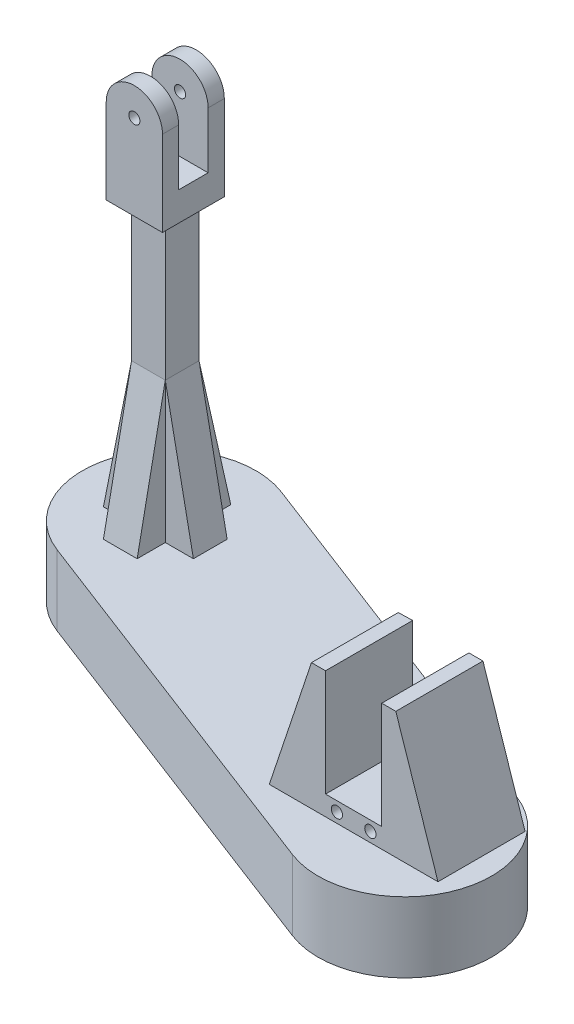
SolidWorks part; units mm, degrees
ref_plane "前基準面" through (0, 0, 0) normal (0, 0, 1) x (1, 0, 0)
ref_plane "上基準面" through (0, 0, 0) normal (0, 1, 0) x (1, 0, 0)
ref_plane "右基準面" through (0, 0, 0) normal (1, 0, 0) x (0, 0, -1)
sketch "草圖1" plane through (0, 0, 0) normal (0, 0, 1) x (1, 0, 0)
  line L0 (0, 0) -> (0, -11.05)
  line L1 (-10, 0) -> (-10, -30.2764)
  line L3 (10, -30.2764) -> (10, 0)
  line L4 (-10, -30.2764) -> (10, -30.2764)
  circle A1 centre (0, 0) radius 1.985
  arc A2 (10, 0) -> (-10, 0) centre (0, 0) ccw
  dimension "D1" = 11.05
  dimension "D2" = 3.97
  dimension "D3" = 20
extrude "填料-伸長1" add sketch "草圖1" along normal blind 12 contours L3 A2 L1 A1 region at (0, -11.3298, 0)
sketch "草圖2" plane through (10, 0, 0) normal (1, 0, 0) x (0, 0, -1)
  line L0 (-12, 0) -> (-9.1, 0)
  line L1 (-12, 0) -> (0, 0) construction
  line L2 (-12, 10) -> (-12, 0) construction
  line L3 (0, 0) -> (-2.9, 0)
  line L4 (-6, 0) -> (-3, 0)
  line L5 (-6, 0) -> (-9, 0)
  line L6 (-9, 0) -> (-9, 15.7808)
  line L7 (-9, 15.7808) -> (-3, 15.7808)
  line L8 (-3, 15.7808) -> (-3, 0)
  line L9 (-3, 0) -> (-3, -20)
  line L10 (-9, 0) -> (-8.6005, -20)
  line L11 (-8.6005, -20) -> (-3, -20)
  line M8 (0, 0) -> (-12, 0)
  dimension "D1" = 2.9
  dimension "D2" = 2.9
  dimension "D3" = 3
  dimension "D4" = 3
  dimension "D5" = 20
extrude "除料-伸長1" cut sketch "草圖2" against normal through all contours L8 L7 L6 M8 | L10 L11 L9 M8 region at (10, 7.8904, 6) region at (10, -9.8852, 5.9013)
sketch "草圖11" plane through (10, 0, 0) normal (1, 0, 0) x (0, 0, -1)
  line L0 (-9, 0) -> (-9, -20)
  line L1 (-9, -20) -> (-8.6005, -20)
  line L2 (-9, 0) -> (-8.6005, -20)
extrude "除料-伸長6" cut sketch "草圖11" against normal through all
sketch "草圖12" plane through (0, 0, 12) normal (0, 0, 1) x (1, 0, 0)
  line L0 (-10, 0) -> (-10, -30.2764)
  line L1 (-10, -30.2764) -> (10, -30.2764)
  line L2 (10, -30.2764) -> (10, 0)
  circle A0 centre (0, 0) radius 1.45
  circle A1 centre (0, 0) radius 10
  circle M1 centre (0, 0) radius 1.985
  line M2 (10, -30.2764) -> (10, 0)
  arc M3 (10, 0) -> (-10, 0) centre (0, 0) ccw
  line M4 (-10, 0) -> (-10, -30.2764)
  line M5 (-10, -30.2764) -> (10, -30.2764)
extrude "填料-伸長11" add sketch "草圖12" along normal blind 5 contours A1 M3 M1 | A1 M4 M5 M2 region at (0, -18.9541, 12) region at (0, 9.7172, 12)
sketch "草圖13" plane through (0, 0, 0) normal (0, 0, -1) x (-1, 0, 0)
  line L0 (-10, 0) -> (-10, -30.2764)
  line L1 (-10, -30.2764) -> (10, -30.2764)
  line L2 (10, 0) -> (10, -30.2764) construction
  line L3 (10, -30.2764) -> (-10, -30.2764) construction
  line L4 (10, -30.2764) -> (10, 0)
  circle A0 centre (0, 0) radius 1.45
  circle A1 centre (0, 0) radius 10
  circle M1 centre (0, 0) radius 1.985
  line M2 (-10, 0) -> (-10, -30.2764)
  line M3 (-10, -30.2764) -> (10, -30.2764)
  line M4 (10, -30.2764) -> (10, 0)
  arc M5 (10, 0) -> (-10, 0) centre (0, 0) ccw
extrude "填料-伸長12" add sketch "草圖13" along normal blind 5 contours A1 M5 M1 | A1 M2 M3 M4 region at (0, -18.9541, 0) region at (0, 9.7172, 0)
sketch "草圖14" plane through (-10, 0, 0) normal (-1, 0, 0) x (0, 0, 1)
  line L0 (3, -20) -> (0.96, -20)
  line L1 (0.96, -20) -> (0.96, 10)
  line L2 (3, 10) -> (-5, 10) construction
  line L3 (0.96, 10) -> (3, 10)
  line L5 (3, 10) -> (11.04, 10)
  line L6 (9, -20) -> (11.04, -20)
  line L7 (11.04, -20) -> (11.04, 10)
  line L8 (17, 10) -> (9, 10) construction
  line L9 (0.96, 10) -> (11.04, 10)
  line L10 (11.04, -20) -> (0.96, -20)
  line L11 (0.96, 10) -> (0.96, -20)
  line L12 (0.96, 10) -> (11.04, 10)
  line M7 (9, 0) -> (9, -20)
  line M8 (9, -20) -> (3, -20)
  line M9 (3, -20) -> (3, 0)
  line M10 (3, 0) -> (-5, 0)
  line M14 (17, 0) -> (9, 0)
  dimension "D1" = 2.04
  dimension "D2" = 2.04
extrude "除料-伸長7" cut sketch "草圖14" against normal through all contours L7 L5 L3 L1 M14 M10 M9 M8 M7 | L1 L0 M9 M10 | L6 L7 M14 M7 region at (-10, -3.1522, 6) region at (-10, -10, 1.98) region at (-10, -10, 10.02)
sketch "草圖15" plane through (0, -30.2764, 0) normal (0, -1, 0) x (1, 0, 0)
  line L0 (-10, 6) -> (10, 6)
  line L1 (-10, 17) -> (-10, -5) construction
  line L2 (10, 17) -> (10, -5) construction
  line L3 (0, 17) -> (0, -5)
  line L4 (-10, 17) -> (10, 17) construction
  line L5 (10, -5) -> (-10, -5) construction
  line L7 (-6, 0) -> (6, 0)
  line L8 (-6, 0) -> (-6, 12)
  line L9 (-6, 12) -> (6, 12)
  line L10 (6, 0) -> (6, 12)
  line L11 (-6, 0) -> (6, 12) construction
  line L12 (-6, 12) -> (6, 0) construction
  point P12 (0, 6)
  dimension "D1" = 12
  dimension "D2" = 12
extrude "填料-伸長13" add sketch "草圖15" along normal blind 100 contours L0 L10 L9 L3 | L9 L8 L0 L3 | L7 L10 L0 L3 | L8 L7 L3 L0 region at (-3, -30.2764, 9) region at (-3, -30.2764, 3) region at (3, -30.2764, 9) region at (3, -30.2764, 3)
sketch "草圖16" plane through (0, -130.2764, 0) normal (0, -1, 0) x (1, 0, 0)
  line L0 (0, 0) -> (0, 12)
  line L1 (-6, 0) -> (6, 0) construction
  line L2 (-6, 12) -> (6, 12) construction
  line L3 (0.1211, 6) -> (6, 6)
  line L4 (6, 0) -> (6, 12) construction
  line L5 (6, 6) -> (176, 6)
  line L10 (176, 6) -> (176, -54)
  line L11 (176, -54) -> (-61, -54)
  line L12 (-61, -54) -> (-61, 6)
  line L13 (-61, 6) -> (-61, 96)
  line L14 (-61, 96) -> (176, 96)
  line L15 (176, 96) -> (176, 6)
  line L16 (-6, 6) -> (-61, 6)
  line L17 (-6, 0) -> (-6, 12) construction
  point P10 (0, 6)
  line M6 (-6, 12) -> (-6, 0)
  line M7 (-6, 0) -> (6, 0)
  line M8 (6, 0) -> (6, 12)
  line M9 (6, 12) -> (-6, 12)
  dimension "D1" = 170
  dimension "D2" = 55
  dimension "D3" = 60
  dimension "D4" = 90
extrude "填料-伸長14" add sketch "草圖16" along normal blind 25 contours L16 L5 L15 L14 L13 M6 M9 M8 | L16 L12 L11 L10 L5 M6 M8 M7 | L0 M7 M9 M6 | L0 M7 M8 M9 region at (-3, -130.2764, 6) region at (57.7926, -130.2764, -24.1374) region at (0.0134, -130.2764, 6) region at (57.6948, -130.2764, 51.1423)
sketch "草圖17" plane through (0, 0, 12) normal (0, 0, 1) x (1, 0, 0)
  line L0 (0, 0) -> (0, -130.2764)
  line L1 (-6, -130.2764) -> (6, -130.2764) construction
sketch "草圖18" plane through (0, -130.2764, 0) normal (0, 1, 0) x (1, 0, 0)
  line L0 (0, -12) -> (116, -12)
  line L1 (116, -12) -> (137.15, -12)
  line L2 (116, -12) -> (94.85, -12)
  line L15 (0, -12) -> (100, -12)
  line L16 (100, -12) -> (100, -37)
  line L17 (100, -37) -> (90, -37)
  line L18 (100, -37) -> (110, -37)
  line L19 (90, -37) -> (90, -47)
  line L20 (90, -47) -> (110, -47)
  line L21 (110, -47) -> (110, -37)
  dimension "D1" = 100
  dimension "D2" = 25
  dimension "D3" = 10
  dimension "D4" = 10
  dimension "D5" = 10
sketch "草圖30" plane through (0, -130.2764, 0) normal (0, 1, 0) x (1, 0, 0)
  line L0 (0, -12) -> (129, -12)
  line L1 (116, -12) -> (137.15, -12) construction
  line L2 (129, -12) -> (129, -37)
  line L4 (129, -37) -> (139, -37)
  line L5 (129, -37) -> (119, -37)
  line L6 (119, -37) -> (119, -68)
  line L7 (119, -68) -> (139, -68)
  line L8 (139, -68) -> (139, -37)
  dimension "D1" = 129
  dimension "D2" = 10
  dimension "D3" = 10
  dimension "D4" = 31
extrude "填料-伸長19" add sketch "草圖30" along normal blind 7 contours L7 L8 L4 L5 L6 region at (129, -130.2764, 52.5)
sketch "草圖31" plane through (0, -130.2764, 0) normal (0, 1, 0) x (1, 0, 0)
  line L0 (119, -68) -> (114, -68)
  line L1 (114, -68) -> (114, -37.1297)
  line L2 (114, -37.1297) -> (119, -37)
  line L3 (119, -37) -> (119, -68)
  line L4 (139, -37) -> (139, -68)
  line L5 (139, -68) -> (144, -68)
  line L6 (144, -68) -> (144, -37)
  line L7 (144, -37) -> (139, -37)
  dimension "D1" = 5
  dimension "D2" = 5
extrude "填料-伸長20" add sketch "草圖31" along normal blind 45 contours L3 L0 L1 L2 | L7 L4 L5 L6
sketch "草圖33" plane through (0, 0, 68) normal (0, 0, 1) x (1, 0, 0)
  line L0 (114, -85.2764) -> (99, -130.2764)
  line L1 (0, -130.2764) -> (100, -130.2764) construction
  line L2 (99, -130.2764) -> (114, -130.2764)
  line L3 (0, -130.2764) -> (116, -130.2764) construction
  line L4 (116, -130.2764) -> (94.85, -130.2764) construction
  line L5 (114, -130.2764) -> (114, -85.2764)
  line L6 (144, -85.2764) -> (159, -130.2764)
  line L7 (-61, -130.2764) -> (176, -130.2764) construction
  line L8 (159, -130.2764) -> (144, -130.2764)
  line L9 (144, -85.2764) -> (144, -130.2764) construction
  line M4 (144, -130.2764) -> (144, -85.2764)
  line M10 (114, -85.2764) -> (114, -130.2764)
  dimension "D1" = 15
  dimension "D2" = 15
extrude "填料-伸長21" add sketch "草圖33" against normal blind 31 contours L8 L6 M4 | L0 L2 M10 region at (109, -115.2764, 68) region at (149, -115.2764, 68)
sketch "草圖35" plane through (0, 0, 37) normal (0, 0, -1) x (-1, 0, 0)
  line L0 (-139, -123.2764) -> (-139, -130.2764)
  line L1 (-119, -130.2764) -> (-159, -130.2764) construction
  line L2 (-139, -130.2764) -> (-119, -130.2764)
  line L3 (-119, -130.2764) -> (-119, -123.2764)
  line L4 (-119, -123.2764) -> (-139, -123.2764)
  line L5 (-139, -126.7764) -> (-119, -126.7764)
  line L6 (-129, -130.2764) -> (-129, -123.2764)
  circle A0 centre (-134.95, -126.7764) radius 2
  circle A1 centre (-123.05, -126.7764) radius 2
  point P15 (-129, -126.7764)
  dimension "D1" = 4
  dimension "D2" = 4
  dimension "D3" = 11.9
  dimension "D4" = 5.95
extrude "除料-伸長16" cut sketch "草圖35" against normal through all contours L5 A0 | L5 A0 | L5 A1 | L5 A1 region at (134.95, -125.9276, 37) region at (134.95, -127.6252, 37) region at (123.05, -125.9276, 37) region at (123.05, -127.6252, 37)
sketch "草圖37" plane through (0, -130.2764, 0) normal (0, 1, 0) x (1, 0, 0)
  line L0 (129, -68) -> (0, -68)
  line L1 (119, -68) -> (139, -68) construction
  dimension "D1" = 129
sketch "草圖38" plane through (-10, 0, 0) normal (-1, 0, 0) x (0, 0, 1)
  line L0 (0.96, 10) -> (0.76, 10)
  line L1 (0.96, 10) -> (-5, 10) construction
  line L2 (11.04, 10) -> (11.24, 10)
  line L3 (17, 10) -> (11.04, 10) construction
  line L4 (0.76, 10) -> (0.76, -20)
  line L5 (0.76, -20) -> (11.24, -20)
  line L6 (11.24, -20) -> (11.24, 10)
  line L7 (0.76, 10) -> (11.24, 10)
  line M3 (0.96, -20) -> (0.96, 0)
  line M4 (0.96, 0) -> (-5, 0)
  line M8 (17, 0) -> (11.04, 0)
  line M9 (11.04, 0) -> (11.04, -20)
  line M10 (11.04, -20) -> (0.96, -20)
  dimension "D1" = 0.2
  dimension "D2" = 0.2
extrude "除料-伸長18" cut sketch "草圖38" against normal through all contours L7 L0 L4 L6 L2 M4 M3 M10 M9 M8 | L4 L5 M3 M4 | L5 L6 M8 M9 region at (-10, -4.8695, 6) region at (-10, -10, 0.86) region at (-10, -10, 11.14)
fillet "圓角2" radius 10 4 edges at (176, -142.7764, -54) (176, -142.7764, 96) (-61, -142.7764, -54) (-61, -142.7764, 96)
sketch "草圖39" plane through (0, 0, 0) normal (0, 0, -1) x (-1, 0, 0)
  line L0 (-6, -80.2764) -> (-16, -130.2764)
  line L1 (-6, -130.2764) -> (-6, -30.2764) construction
  line L2 (0, -130.2764) -> (-116, -130.2764) construction
  line L3 (-16, -130.2764) -> (-6, -130.2764)
  line L4 (-6, -130.2764) -> (-6, -80.2764)
  line L6 (6, -80.2764) -> (16, -130.2764)
  line L7 (6, -130.2764) -> (6, -30.2764) construction
  line L8 (-166, -130.2764) -> (51, -130.2764) construction
  line L9 (16, -130.2764) -> (6, -130.2764)
  line L10 (6, -130.2764) -> (6, -80.2764)
  dimension "D1" = 50
  dimension "D2" = 10
  dimension "D3" = 10
extrude "填料-伸長22" add sketch "草圖39" against normal blind 12
sketch "草圖40" plane through (6, 0, 0) normal (1, 0, 0) x (0, 0, -1)
  line L0 (-12, -80.2764) -> (-22, -130.2764)
  line L1 (-12, -130.2764) -> (-37, -130.2764) construction
  line L2 (-22, -130.2764) -> (-12, -130.2764)
  line L3 (-12, 0) -> (-12, -130.2764) construction
  line L4 (-12, -130.2764) -> (-12, -80.2764)
  line L5 (0, -80.2764) -> (11.3032, -130.2764)
  line L6 (-86, -130.2764) -> (44, -130.2764) construction
  line L7 (11.3032, -130.2764) -> (0, -130.2764)
  line L8 (0, -130.2764) -> (0, -80.2764)
  dimension "D1" = 10
extrude "填料-伸長23" add sketch "草圖40" against normal blind 12
sketch "草圖43" plane through (0, -130.2764, 0) normal (0, 1, 0) x (1, 0, 0)
  line L0 (0, -4.6155) -> (135.9213, -56.7097) construction
  line L1 (11.053, 24.2233) -> (146.9743, -27.8709)
  line L2 (-11.053, -33.4544) -> (124.8684, -85.5486)
  line L4 (-74.976, 67.6441) -> (186.8952, 67.6441)
  line L5 (-74.976, 67.6441) -> (-74.976, -109.084)
  line L6 (-74.976, -109.084) -> (186.8952, -109.084)
  line L7 (186.8952, 67.6441) -> (186.8952, -109.084)
  arc A0 (11.053, 24.2233) -> (-11.053, -33.4544) centre (0, -4.6155) ccw
  arc A1 (124.8684, -85.5486) -> (146.9743, -27.8709) centre (135.9213, -56.7097) ccw
  point P2 (67.9607, -30.6626)
extrude "除料-伸長19" cut sketch "草圖43" against normal through all
